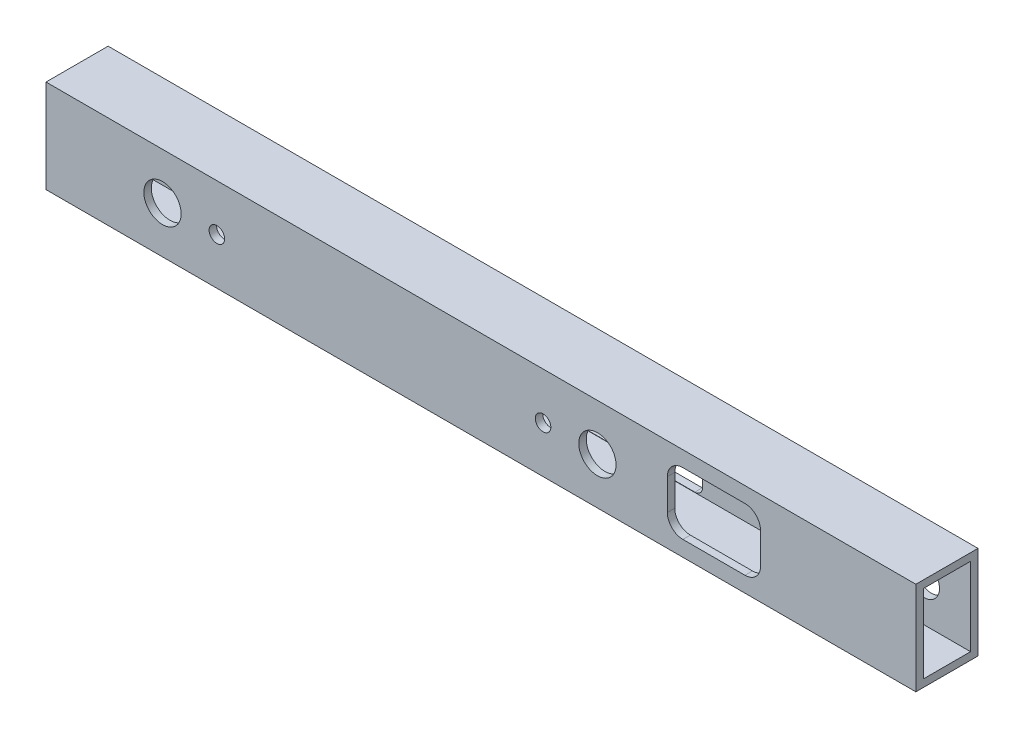
SolidWorks part; units mm, degrees
material "AISI 1010 Steel, hot rolled bar"
ref_plane "Front Plane" through (0, 0, 0) normal (0, 0, 1) x (1, 0, 0)
ref_plane "Top Plane" through (0, 0, 0) normal (0, 1, 0) x (1, 0, 0)
ref_plane "Right Plane" through (0, 0, 0) normal (1, 0, 0) x (0, 0, -1)
sketch "Sketch1" plane through (0, 0, 0) normal (1, 0, 0) x (0, 0, -1)
  line L0 (-9.652, 16.002) -> (9.652, 16.002)
  line L1 (-12.7, -19.05) -> (12.7, -19.05)
  line L2 (-12.7, -19.05) -> (-12.7, 19.05)
  line L3 (-12.7, 19.05) -> (12.7, 19.05)
  line L4 (12.7, -19.05) -> (12.7, 19.05)
  line L5 (-12.7, -19.05) -> (12.7, 19.05) construction
  line L6 (-12.7, 19.05) -> (12.7, -19.05) construction
  line L7 (9.652, -16.002) -> (9.652, 16.002)
  line L8 (-9.652, -16.002) -> (9.652, -16.002)
  line L9 (-9.652, -16.002) -> (-9.652, 16.002)
  point P0 (0, 0)
  dimension "D1" = 25.4
  dimension "D2" = 38.1
  dimension "D3" = 3.048
extrude "Boss-Extrude1" add sketch "Sketch1" along normal blind 355.6
sketch "Sketch2" plane through (0, 0, -12.7) normal (0, 0, -1) x (-1, 0, 0)
  line L0 (-355.6, 0) -> (0, 0) construction
  line L1 (-355.6, -19.05) -> (-355.6, 19.05) construction
  circle A0 centre (-336.55, 0) radius 6.35
  dimension "D2" = 12.7
  dimension "D1" = 19.05
extrude "Cut-Extrude1" cut sketch "Sketch2" against normal up to next
sketch "Sketch3" plane through (0, 0, -12.7) normal (0, 0, -1) x (-1, 0, 0)
  line L0 (0, 0) -> (-355.6, 0) construction
  line L1 (-355.6, -19.05) -> (-355.6, 19.05) construction
  circle A0 centre (-266.7, 0) radius 3.175
  circle A1 centre (-336.55, 0) radius 6.35 construction
  dimension "D1" = 69.85
  dimension "D2" = 6.35
extrude "Cut-Extrude2" cut sketch "Sketch3" against normal up to next
sketch "Sketch4" plane through (0, 0, 12.7) normal (0, 0, 1) x (1, 0, 0)
  line L0 (0, 0) -> (355.6, 0) construction
  line L1 (260.35, -12.7) -> (285.75, -12.7)
  line L2 (254, -6.35) -> (254, 6.35)
  line L3 (260.35, 12.7) -> (285.75, 12.7)
  line L4 (292.1, -6.35) -> (292.1, 6.35)
  line L5 (254, -12.7) -> (292.1, 12.7) construction
  line L6 (254, 12.7) -> (292.1, -12.7) construction
  line L7 (355.6, 19.05) -> (355.6, -19.05) construction
  arc A0 (285.75, 12.7) -> (292.1, 6.35) centre (285.75, 6.35) cw
  arc A1 (285.75, -12.7) -> (292.1, -6.35) centre (285.75, -6.35) ccw
  arc A2 (260.35, -12.7) -> (254, -6.35) centre (260.35, -6.35) cw
  arc A3 (254, 6.35) -> (260.35, 12.7) centre (260.35, 6.35) cw
  point P0 (273.05, 0)
  dimension "D4" = 6.35
  dimension "D1" = 38.1
  dimension "D2" = 25.4
  dimension "D3" = 63.5
extrude "Cut-Extrude3" cut sketch "Sketch4" against normal up to next
sketch "Sketch5" plane through (0, 0, 12.7) normal (0, 0, 1) x (1, 0, 0)
  line L0 (47.625, 19.05) -> (47.625, -19.05) construction
  line L1 (355.6, 19.05) -> (0, 19.05) construction
  line L2 (355.6, -19.05) -> (0, -19.05) construction
  line L3 (31.75, 0) -> (63.5, 0) construction
  line L4 (0, 19.05) -> (0, -19.05) construction
  line L5 (225.425, 19.05) -> (225.425, -19.05) construction
  line L6 (209.55, 0) -> (241.3, 0) construction
  circle A0 centre (47.625, 0) radius 7.62
  circle A1 centre (225.425, 0) radius 7.62
  point P8 (47.625, 0)
  point P18 (225.425, 0)
  dimension "D2" = 15.24
  dimension "D6" = 15.24
  dimension "D1" = 47.625
  dimension "D3" = 31.75
  dimension "D4" = 225.425
  dimension "D5" = 31.75
extrude "Cut-Extrude4" cut sketch "Sketch5" against normal up to next
sketch "Sketch6" plane through (0, 0, 12.7) normal (0, 0, 1) x (1, 0, 0)
  line L0 (47.625, 0) -> (225.425, 0) construction
  line L1 (69.85, 0) -> (69.85, 8.5) construction
  line L2 (203.2, 8.5) -> (203.2, -8.5) construction
  line L3 (69.85, 0) -> (69.85, -8.5) construction
  circle A0 centre (69.85, 0) radius 3.175
  circle A1 centre (203.2, 0) radius 3.175
  point P8 (0, 0)
  point P9 (0, 0)
  dimension "D2" = 6.35
  dimension "D5" = 6.35
  dimension "D3" = 22.225
  dimension "D1" = 17
  dimension "D4" = 17
  dimension "D6" = 22.225
extrude "Cut-Extrude5" cut sketch "Sketch6" against normal up to next
sketch "Sketch7" plane through (0, 0, -12.7) normal (0, 0, -1) x (-1, 0, 0)
  line L0 (0, 0) -> (-355.6, 0) construction
  line L1 (-242.8875, -15.875) -> (-185.7375, -15.875)
  line L2 (-246.0625, -12.7) -> (-246.0625, 12.7)
  line L3 (-242.8875, 15.875) -> (-185.7375, 15.875)
  line L4 (-182.5625, -12.7) -> (-182.5625, 12.7)
  line L5 (-246.0625, -15.875) -> (-182.5625, 15.875) construction
  line L6 (-246.0625, 15.875) -> (-182.5625, -15.875) construction
  line L7 (-87.3125, -15.875) -> (-30.1625, -15.875)
  line L8 (-90.4875, -12.7) -> (-90.4875, 12.7)
  line L9 (-87.3125, 15.875) -> (-30.1625, 15.875)
  line L10 (-26.9875, -12.7) -> (-26.9875, 12.7)
  line L11 (-90.4875, -15.875) -> (-26.9875, 15.875) construction
  line L12 (-90.4875, 15.875) -> (-26.9875, -15.875) construction
  line L13 (-355.6, -19.05) -> (-355.6, 19.05) construction
  line L14 (-214.3125, 0) -> (-214.3125, 15.875) construction
  line L15 (-58.7375, 0) -> (-58.7375, 15.875) construction
  circle A0 centre (-69.85, 0) radius 3.175 construction
  circle A1 centre (-47.625, 0) radius 7.62 construction
  circle A2 centre (-203.2, 0) radius 3.175 construction
  circle A3 centre (-225.425, 0) radius 7.62 construction
  circle A4 centre (-69.85, 0) radius 3.175 construction
  circle A5 centre (-47.625, 0) radius 7.62 construction
  circle A6 centre (-203.2, 0) radius 3.175 construction
  circle A7 centre (-225.425, 0) radius 7.62 construction
  arc A8 (-26.9875, -12.7) -> (-30.1625, -15.875) centre (-30.1625, -12.7) cw
  arc A9 (-87.3125, -15.875) -> (-90.4875, -12.7) centre (-87.3125, -12.7) cw
  arc A10 (-26.9875, 12.7) -> (-30.1625, 15.875) centre (-30.1625, 12.7) ccw
  arc A11 (-87.3125, 15.875) -> (-90.4875, 12.7) centre (-87.3125, 12.7) ccw
  arc A12 (-246.0625, -12.7) -> (-242.8875, -15.875) centre (-242.8875, -12.7) ccw
  arc A13 (-185.7375, -15.875) -> (-182.5625, -12.7) centre (-185.7375, -12.7) ccw
  arc A14 (-182.5625, 12.7) -> (-185.7375, 15.875) centre (-185.7375, 12.7) ccw
  arc A15 (-242.8875, 15.875) -> (-246.0625, 12.7) centre (-242.8875, 12.7) ccw
  point P0 (-214.3125, 0)
  point P5 (-58.7375, 0)
  point P29 (0, 0)
  dimension "D4" = 3.175
  dimension "D1" = 31.75
  dimension "D2" = 63.5
  dimension "D3" = 63.5
extrude "Cut-Extrude6" cut sketch "Sketch7" against normal up to next
equation "\"D5@Sketch5\"=\"D3@Sketch5\""
equation "\"D6@Sketch5\"=\"D2@Sketch5\""
equation "\"D4@Sketch6\"=\"D1@Sketch6\""
equation "\"D5@Sketch6\"=\"D2@Sketch6\""
equation "\"D6@Sketch6\"=\"D3@Sketch6\""
equation "\"D3@Sketch7\"=\"D2@Sketch7\""
